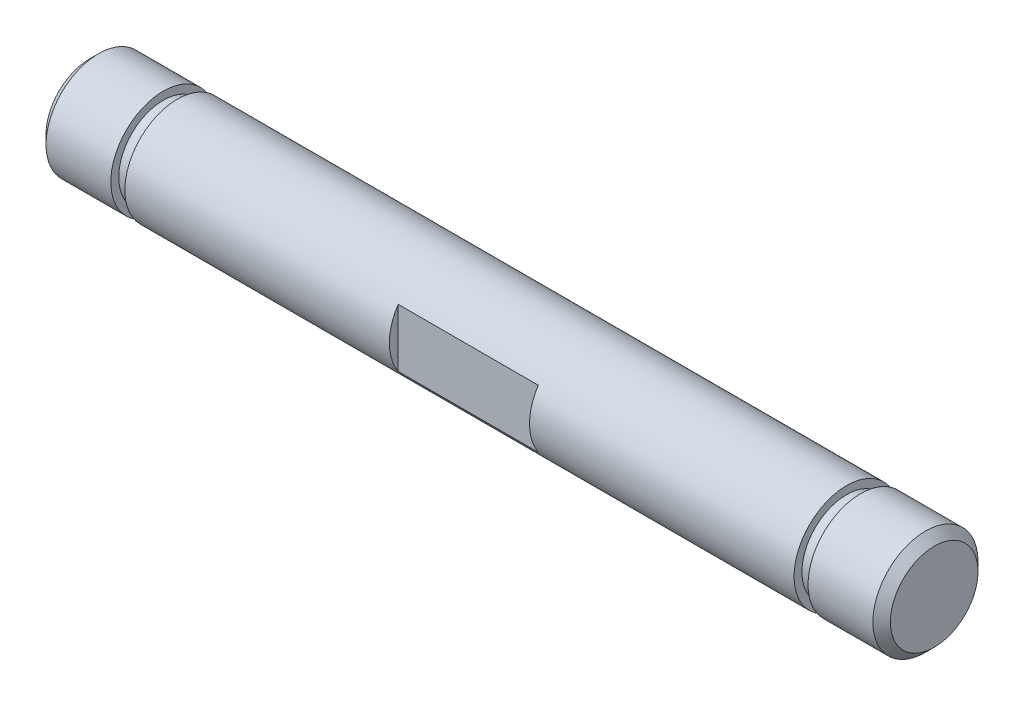
SolidWorks part; units mm, degrees
ref_plane "Alzado" through (0, 0, 0) normal (1, 0, 0) x (0, 1, 0)
ref_plane "Planta" through (0, 0, 0) normal (0, 0, 1) x (0, 1, 0)
ref_plane "Vista lateral" through (0, 0, 0) normal (0, 1, 0) x (-1, 0, 0)
sketch "Croquis1" plane through (0, 0, 0) normal (0, 1, 0) x (-1, 0, 0)
  line L1 (-19.1, 3) -> (19.1, 3)
  line L6 (24.1, 3) -> (24.1, 0)
  line L7 (-24.1, 0) -> (24.1, 0) construction
  line L22 (-24.1, 0) -> (24.1, 0)
  line L23 (19.1, 3) -> (19.1, 2.55)
  line L24 (19.1, 2.55) -> (19.9, 2.55)
  line L25 (19.9, 2.55) -> (19.9, 3)
  line L26 (19.9, 3) -> (24.1, 3)
  line L27 (0, 0) -> (0, 3) construction
  line L28 (-19.9, 3) -> (-24.1, 3)
  line L29 (-19.9, 2.55) -> (-19.9, 3)
  line L30 (-19.1, 2.55) -> (-19.9, 2.55)
  line L31 (-19.1, 3) -> (-19.1, 2.55)
  line L32 (-24.1, 3) -> (-24.1, 0)
  dimension "D1" = 5
  dimension "D2" = 6
  dimension "D3" = 38.2
  dimension "D4" = 0.8
  dimension "D7" = 0.45
revolve "Revolución1" add sketch "Croquis1" angle 360 about L7
sketch "Croquis2" plane through (0, 0, 0) normal (1, 0, 0) x (0, 1, 0)
  line L1 (1.6583, 2.5) -> (-1.6583, 2.5)
  circle A0 centre (0, 0) radius 3 construction
  circle A1 centre (0, 0) radius 3
  arc A3 (1.6583, 2.5) -> (-1.6583, 2.5) centre (0, 0) ccw
  point P4 (0, 3)
  dimension "D2" = 0.5
  dimension "D1" = 0
extrude "Cortar-Extruir1" cut sketch "Croquis2" against normal mid plane 8
chamfer "Chaflán1" distance 0.5 angle 45 2 edges at (-24.1, 0, -3) (24.1, 0, -3)
equation "\"ancho_circlip\"=0.8"
equation "\"ranura_circlip\"=0.45"
